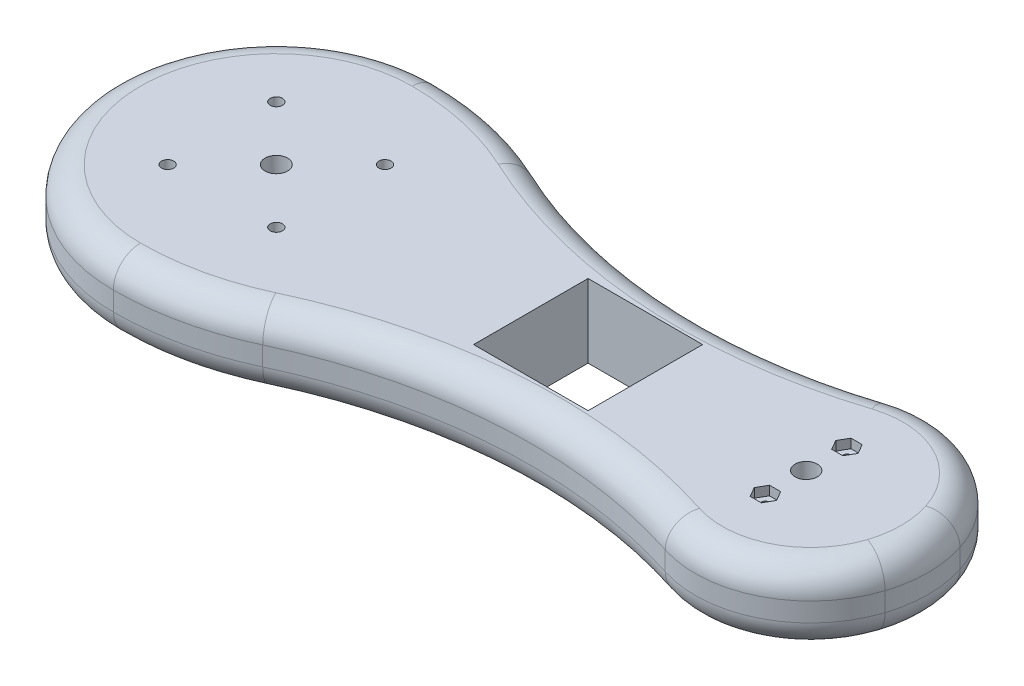
SolidWorks part; units mm, degrees
material "PLA"
ref_plane "Front Plane" through (0, 0, 0) normal (0, 0, 1) x (1, 0, 0)
ref_plane "Top Plane" through (0, 0, 0) normal (0, 1, 0) x (1, 0, 0)
ref_plane "Right Plane" through (0, 0, 0) normal (1, 0, 0) x (0, 0, -1)
other "Centro de masa"
sketch "Sketch1" plane through (0, 0, 0) normal (0, 1, 0) x (1, 0, 0)
  line L0 (0, 60) -> (0, -60) construction
  line L3 (0, 0) -> (195, 0) construction
  line L4 (195, 45) -> (195, -45) construction
  line L5 (0, 50) -> (-33.1662, 50) construction
  line L7 (-20, 20) -> (20, 20) construction
  line L8 (-20, 20) -> (-20, -20) construction
  line L9 (-20, -20) -> (20, -20) construction
  line L10 (20, 20) -> (20, -20) construction
  line L11 (-20, 20) -> (20, -20) construction
  line L12 (-20, -20) -> (20, 20) construction
  line L13 (93.67, -21.07) -> (135.81, -21.07)
  line L14 (93.67, -21.07) -> (93.67, 21.07)
  line L15 (93.67, 21.07) -> (135.81, 21.07)
  line L16 (135.81, -21.07) -> (135.81, 21.07)
  line L17 (93.67, -21.07) -> (135.81, 21.07) construction
  line L18 (93.67, 21.07) -> (135.81, -21.07) construction
  arc A4 (0, 60) -> (0, -60) centre (0, 0) ccw
  arc A5 (195, -45) -> (195, 45) centre (195, 0) ccw
  arc A6 (0, 60) -> (45, 50) centre (0, -46.25) cw
  arc A7 (45, 50) -> (195, 45) centre (125.8475, 222.9237) ccw
  circle A10 centre (-20, -20) radius 2.25
  circle A11 centre (20, -20) radius 2.25
  circle A12 centre (-20, 20) radius 2.25
  circle A13 centre (20, 20) radius 2.25
  circle A14 centre (0, 0) radius 4.15
  circle A15 centre (195, 0) radius 4.09
  circle A16 centre (195, -15) radius 1.6
  circle A17 centre (195, 15) radius 1.6
  arc A18 (0, -60) -> (45, -50) centre (0, 46.25) ccw
  arc A19 (45, -50) -> (195, -45) centre (125.8475, -222.9237) cw
  point P27 (114.74, 0)
  dimension "D1" = 120
  dimension "D2" = 195
  dimension "D4" = 10
  dimension "D5" = 45
  dimension "D3" = 90
  dimension "D7" = 4.5
  dimension "D8" = 8.3
  dimension "D9" = 8.18
  dimension "D10" = 3.2
  dimension "D6" = 40
  dimension "D11" = 15
  dimension "D12" = 15
  dimension "D13" = 42.14
  dimension "D14" = 59.19
extrude "Saliente-Extruir1" add sketch "Sketch1" along normal blind 27
fillet "Redondeo1" radius 42.5 2 edges at (195, 13.5, -45) (195, 13.5, 45)
fillet "Redondeo2" radius 10 16 edges at (23.0489, 27, 57.4699) (-60, 27, 0) (23.0489, 27, -57.4699) (113.8454, 27, -32.4116) (216.7747, 27, -38.5827) (240, 27, 0) (216.7747, 27, 38.5827) (23.0489, 0, 57.4699) (-60, 0, 0) (23.0489, 0, -57.4699) (113.8454, 0, -32.4116) (216.7747, 0, -38.5827) (240, 0, 0) (216.7747, 0, 38.5827) (113.8454, 27, 32.4116) (113.8454, 0, 32.4116)
sketch "Croquis1" plane through (0, 0, 0) normal (0, -1, 0) x (1, 0, 0)
  line L0 (195, 17.4) -> (195, -17.4) construction
  line L1 (207.7, 17.4) -> (207.7, -17.4)
  line L2 (182.3, 17.4) -> (182.3, -17.4)
  arc A0 (207.7, 17.4) -> (182.3, 17.4) centre (195, 17.4) ccw
  arc A1 (182.3, -17.4) -> (207.7, -17.4) centre (195, -17.4) ccw
  point P2 (195, 0)
  point P11 (195, -30.1)
  point P12 (195, 30.1)
  dimension "D1" = 12.7
  dimension "D2" = 60.2
extrude "Cortar-Extruir1" cut sketch "Croquis1" against normal blind 10.2
ref_point "Punto1"
sketch "Croquis2" plane through (0, 27, 0) normal (0, 1, 0) x (1, 0, 0)
  line L1 (199.1107, 15) -> (197.0554, 18.56)
  line L2 (197.0554, 18.56) -> (192.9446, 18.56)
  line L3 (192.9446, 18.56) -> (190.8893, 15)
  line L4 (190.8893, 15) -> (192.9446, 11.44)
  line L5 (192.9446, 11.44) -> (197.0554, 11.44)
  line L6 (197.0554, 11.44) -> (199.1107, 15)
  line L7 (197.0554, -11.44) -> (192.9446, -11.44)
  line L8 (192.9446, -11.44) -> (190.8893, -15)
  line L9 (190.8893, -15) -> (192.9446, -18.56)
  line L10 (192.9446, -18.56) -> (197.0554, -18.56)
  line L11 (197.0554, -18.56) -> (199.1107, -15)
  line L12 (199.1107, -15) -> (197.0554, -11.44)
  circle A0 centre (195, 15) radius 3.56 construction
  circle A1 centre (195, -15) radius 3.56 construction
  dimension "D1" = 7.12
extrude "Cortar-Extruir2" cut sketch "Croquis2" against normal blind 3.39
